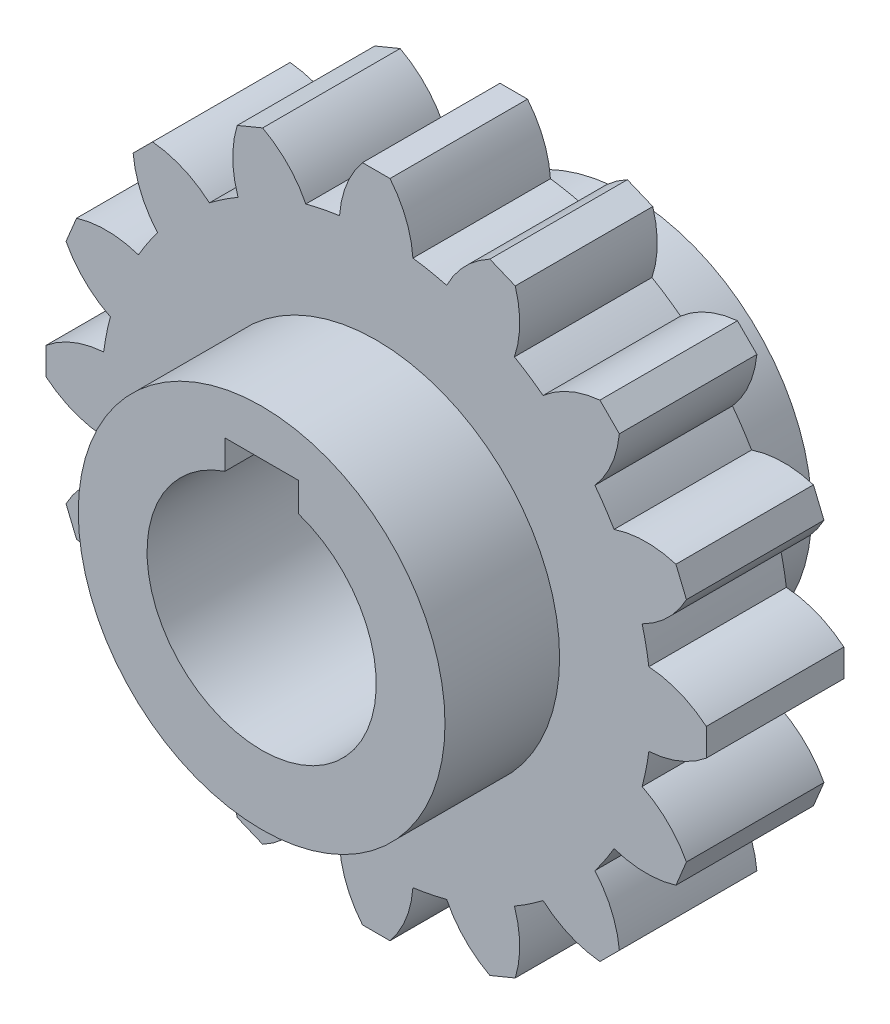
SolidWorks part; units mm, degrees
ref_plane "Front Plane" through (0, 0, 0) normal (0, 0, 1) x (1, 0, 0)
ref_plane "Top Plane" through (0, 0, 0) normal (0, 1, 0) x (1, 0, 0)
ref_plane "Right Plane" through (0, 0, 0) normal (1, 0, 0) x (0, 0, -1)
sketch "Sketch1" plane through (0, 0, 0) normal (0, 0, 1) x (1, 0, 0)
  line L0 (0, -40.6806) -> (0, -36) construction
  line L1 (-1.5, 36) -> (1.5, 36)
  line L2 (12.3908, 33.8337) -> (15.1624, 32.6856)
  line L3 (24.3952, 26.5165) -> (26.5165, 24.3952)
  line L4 (32.6856, 15.1624) -> (33.8337, 12.3908)
  line L5 (36, 1.5) -> (36, -1.5)
  line L6 (33.8337, -12.3908) -> (32.6856, -15.1624)
  line L7 (26.5165, -24.3952) -> (24.3952, -26.5165)
  line L8 (15.1624, -32.6856) -> (12.3908, -33.8337)
  line L9 (1.5, -36) -> (-1.5, -36)
  line L10 (-12.3908, -33.8337) -> (-15.1624, -32.6856)
  line L11 (-24.3952, -26.5165) -> (-26.5165, -24.3952)
  line L12 (-32.6856, -15.1624) -> (-33.8337, -12.3908)
  line L13 (-36, -1.5) -> (-36, 1.5)
  line L14 (-33.8337, 12.3908) -> (-32.6856, 15.1624)
  line L15 (-26.5165, 24.3952) -> (-24.3952, 26.5165)
  line L16 (-15.1624, 32.6856) -> (-12.3908, 33.8337)
  line L17 (0, -30) -> (0, 44.2599) construction
  arc A0 (-4, 29.7321) -> (-7.6825, 28.9996) centre (0, 0) ccw
  arc A1 (1.5, 36) -> (4, 29.7321) centre (-6.9748, 28.9873) cw
  arc A2 (-1.5, 36) -> (-4, 29.7321) centre (6.9748, 28.9873) ccw
  arc A3 (12.3908, 33.8337) -> (7.6825, 28.9996) centre (17.5368, 24.1116) ccw
  arc A4 (15.1624, 32.6856) -> (15.0735, 25.9382) centre (4.6491, 29.4499) cw
  arc A5 (24.3952, 26.5165) -> (18.1954, 23.8522) centre (25.429, 15.5652) ccw
  arc A6 (26.5165, 24.3952) -> (23.8522, 18.1954) centre (15.5652, 25.429) cw
  arc A7 (32.6856, 15.1624) -> (25.9382, 15.0735) centre (29.4499, 4.6491) ccw
  arc A8 (33.8337, 12.3908) -> (28.9996, 7.6825) centre (24.1116, 17.5368) cw
  arc A9 (36, 1.5) -> (29.7321, 4) centre (28.9873, -6.9748) ccw
  arc A10 (36, -1.5) -> (29.7321, -4) centre (28.9873, 6.9748) cw
  arc A11 (33.8337, -12.3908) -> (28.9996, -7.6825) centre (24.1116, -17.5368) ccw
  arc A12 (32.6856, -15.1624) -> (25.9382, -15.0735) centre (29.4499, -4.6491) cw
  arc A13 (26.5165, -24.3952) -> (23.8522, -18.1954) centre (15.5652, -25.429) ccw
  arc A14 (24.3952, -26.5165) -> (18.1954, -23.8522) centre (25.429, -15.5652) cw
  arc A15 (15.1624, -32.6856) -> (15.0735, -25.9382) centre (4.6491, -29.4499) ccw
  arc A16 (12.3908, -33.8337) -> (7.6825, -28.9996) centre (17.5368, -24.1116) cw
  arc A17 (1.5, -36) -> (4, -29.7321) centre (-6.9748, -28.9873) ccw
  arc A18 (-1.5, -36) -> (-4, -29.7321) centre (6.9748, -28.9873) cw
  arc A19 (-12.3908, -33.8337) -> (-7.6825, -28.9996) centre (-17.5368, -24.1116) ccw
  arc A20 (-15.1624, -32.6856) -> (-15.0735, -25.9382) centre (-4.6491, -29.4499) cw
  arc A21 (-24.3952, -26.5165) -> (-18.1954, -23.8522) centre (-25.429, -15.5652) ccw
  arc A22 (-26.5165, -24.3952) -> (-23.8522, -18.1954) centre (-15.5652, -25.429) cw
  arc A23 (-32.6856, -15.1624) -> (-25.9382, -15.0735) centre (-29.4499, -4.6491) ccw
  arc A24 (-33.8337, -12.3908) -> (-28.9996, -7.6825) centre (-24.1116, -17.5368) cw
  arc A25 (-36, -1.5) -> (-29.7321, -4) centre (-28.9873, 6.9748) ccw
  arc A26 (-36, 1.5) -> (-29.7321, 4) centre (-28.9873, -6.9748) cw
  arc A27 (-33.8337, 12.3908) -> (-28.9996, 7.6825) centre (-24.1116, 17.5368) ccw
  arc A28 (-32.6856, 15.1624) -> (-25.9382, 15.0735) centre (-29.4499, 4.6491) cw
  arc A29 (-26.5165, 24.3952) -> (-23.8522, 18.1954) centre (-15.5652, 25.429) ccw
  arc A30 (-24.3952, 26.5165) -> (-18.1954, 23.8522) centre (-25.429, 15.5652) cw
  arc A31 (-15.1624, 32.6856) -> (-15.0735, 25.9382) centre (-4.6491, 29.4499) ccw
  arc A32 (-12.3908, 33.8337) -> (-7.6825, 28.9996) centre (-17.5368, 24.1116) cw
  arc A33 (-15.0735, 25.9382) -> (-18.1954, 23.8522) centre (0, 0) ccw
  arc A34 (-23.8522, 18.1954) -> (-25.9382, 15.0735) centre (0, 0) ccw
  arc A35 (-28.9996, 7.6825) -> (-29.7321, 4) centre (0, 0) ccw
  arc A36 (-29.7321, -4) -> (-28.9996, -7.6825) centre (0, 0) ccw
  arc A37 (-25.9382, -15.0735) -> (-23.8522, -18.1954) centre (0, 0) ccw
  arc A38 (-18.1954, -23.8522) -> (-15.0735, -25.9382) centre (0, 0) ccw
  arc A39 (-7.6825, -28.9996) -> (-4, -29.7321) centre (0, 0) ccw
  arc A40 (4, -29.7321) -> (7.6825, -28.9996) centre (0, 0) ccw
  arc A41 (15.0735, -25.9382) -> (18.1954, -23.8522) centre (0, 0) ccw
  arc A42 (23.8522, -18.1954) -> (25.9382, -15.0735) centre (0, 0) ccw
  arc A43 (28.9996, -7.6825) -> (29.7321, -4) centre (0, 0) ccw
  arc A44 (29.7321, 4) -> (28.9996, 7.6825) centre (0, 0) ccw
  arc A45 (25.9382, 15.0735) -> (23.8522, 18.1954) centre (0, 0) ccw
  arc A46 (18.1954, 23.8522) -> (15.0735, 25.9382) centre (0, 0) ccw
  arc A47 (7.6825, 28.9996) -> (4, 29.7321) centre (0, 0) ccw
  dimension "D1" = 60
  dimension "D3" = 11
  dimension "D2" = 6
  dimension "D4" = 8
  dimension "D5" = 3
  dimension "D6" = 16
extrude "Boss-Extrude1" add sketch "Sketch1" along normal mid plane 15
sketch "Sketch2" plane through (0, 0, 0) normal (0, 0, 1) x (1, 0, 0)
  circle A0 centre (0, 0) radius 20
  dimension "D1" = 40
extrude "Boss-Extrude2" add sketch "Sketch2" along normal mid plane 40
sketch "Sketch3" plane through (0, 0, 20) normal (0, 0, 1) x (1, 0, 0)
  line L0 (0, 16.2332) -> (0, 12.5) construction
  line L1 (-4, 15) -> (-4, 11.8427)
  line L2 (-4, 15) -> (4, 15)
  line L3 (4, 15) -> (4, 11.8427)
  arc A0 (-4, 11.8427) -> (4, 11.8427) centre (0, 0) ccw
  point P6 (-6.7104, 10.4496)
  point P9 (0, 0)
  point P10 (0, 0)
  dimension "D1" = 15
  dimension "D2" = 25
  dimension "D3" = 8
extrude "Cut-Extrude1" cut sketch "Sketch3" against normal through all both and the other way through all
